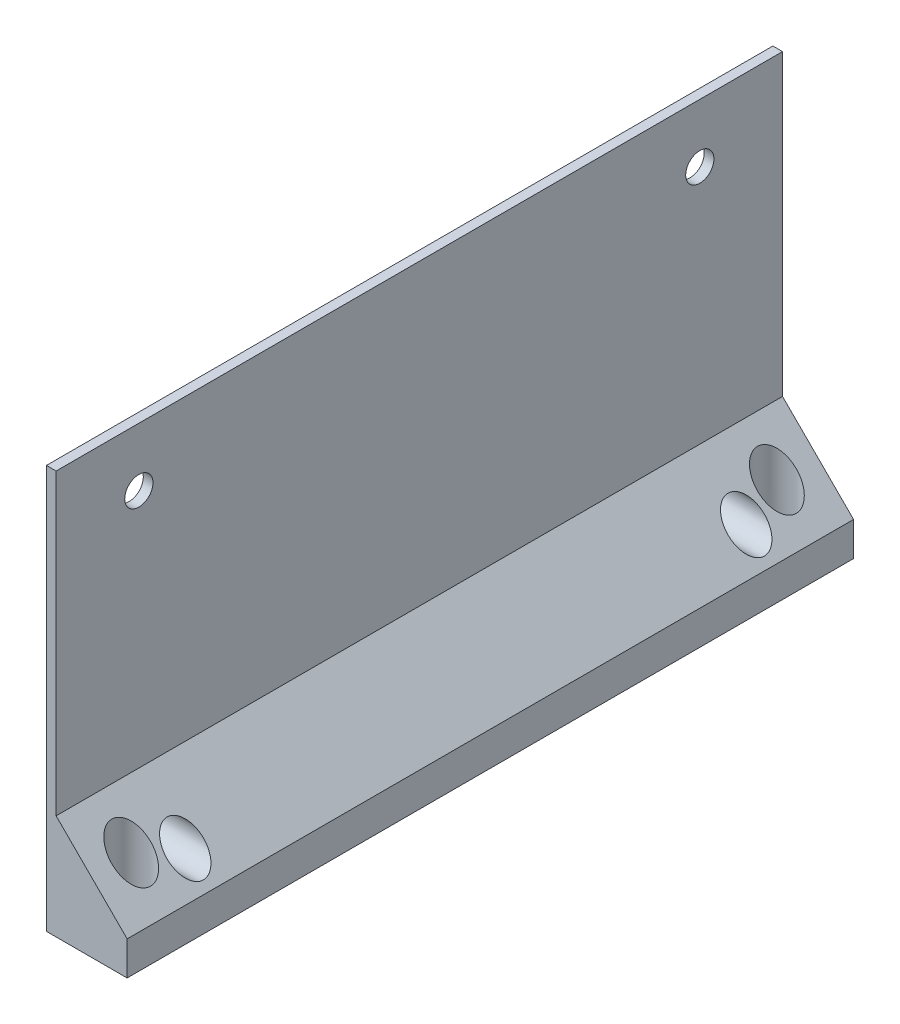
SolidWorks part; units mm, degrees
ref_plane "Plan de face" through (0, 0, 0) normal (0, 0, 1) x (1, 0, 0)
ref_plane "Plan de dessus" through (0, 0, 0) normal (0, 1, 0) x (1, 0, 0)
ref_plane "Plan de droite" through (0, 0, 0) normal (1, 0, 0) x (0, 0, -1)
sketch "Esquisse7" plane through (0, 0, 0) normal (0, 0, 1) x (1, 0, 0)
  line L0 (0, 0) -> (10, 0)
  line L1 (0, 0) -> (0, 50)
  line L2 (1.2, 3) -> (1.2, 50)
  line L3 (1.2, 3) -> (10, 3)
  line L4 (0, 50) -> (1.2, 50)
  line L6 (10, 0) -> (10, 3)
  dimension "D2" = 50
  dimension "D3" = 10
  dimension "D1" = 1.2
  dimension "D4" = 3
  dimension "D5" = 90
extrude "Boss.-Extru.4" add sketch "Esquisse7" along normal blind 90
sketch "Esquisse8" plane through (0, 0, 0) normal (-1, 0, 0) x (0, 0, 1)
  line L0 (0, 50) -> (90, 0) construction
  line L2 (10.25, 7.25) -> (79.75, 7.25) construction
  line L3 (10.25, 7.25) -> (10.25, 42.75) construction
  line L4 (10.25, 42.75) -> (79.75, 42.75) construction
  line L5 (79.75, 7.25) -> (79.75, 42.75) construction
  line L6 (10.25, 7.25) -> (79.75, 42.75) construction
  line L7 (10.25, 42.75) -> (79.75, 7.25) construction
  circle A0 centre (10.25, 42.75) radius 1.75
  circle A1 centre (10.25, 7.25) radius 1.75
  circle A2 centre (79.75, 7.25) radius 1.75
  circle A3 centre (79.75, 42.75) radius 1.75
  point P4 (45, 25)
  dimension "D3" = 3.5
  dimension "D1" = 69.5
  dimension "D2" = 35.5
extrude "Enlèv. mat.-Extru.5" cut sketch "Esquisse8" against normal through all
sketch "Esquisse9" plane through (0, 0, 0) normal (0, -1, 0) x (1, 0, 0)
  line L0 (5.5, 5) -> (5.5, 85) construction
  line L1 (5.5, 45) -> (0, 45) construction
  line L2 (0, 90) -> (0, 0) construction
  line L3 (10, 90) -> (10, 0) construction
  circle A0 centre (5.5, 85) radius 2.4
  circle A1 centre (5.5, 5) radius 2.4
  point P3 (5.5, 45)
  point P9 (10.2843, 45)
  dimension "D3" = 4.8
  dimension "D1" = 80
  dimension "D2" = 4.5
extrude "Enlèv. mat.-Extru.6" cut sketch "Esquisse9" against normal through all
fillet "Congé7" radius 10 1 edges at (1.2, 3, 45) profile chamfer
sketch "Esquisse10" plane through (0, 0, 0) normal (-1, 0, 0) x (0, 0, 1)
  circle A0 centre (79.75, 7.25) radius 1.75 construction
  circle A1 centre (79.75, 7.25) radius 1.75
  circle A2 centre (10.25, 7.25) radius 1.75 construction
  circle A3 centre (10.25, 7.25) radius 1.75
  circle A4 centre (10.25, 7.25) radius 2.25
  circle A5 centre (79.75, 7.25) radius 2.25
  dimension "D1" = 0.5
extrude "Enlèv. mat.-Extru.7" cut sketch "Esquisse10" against normal through all from offset 1.2 offset against normal yes
